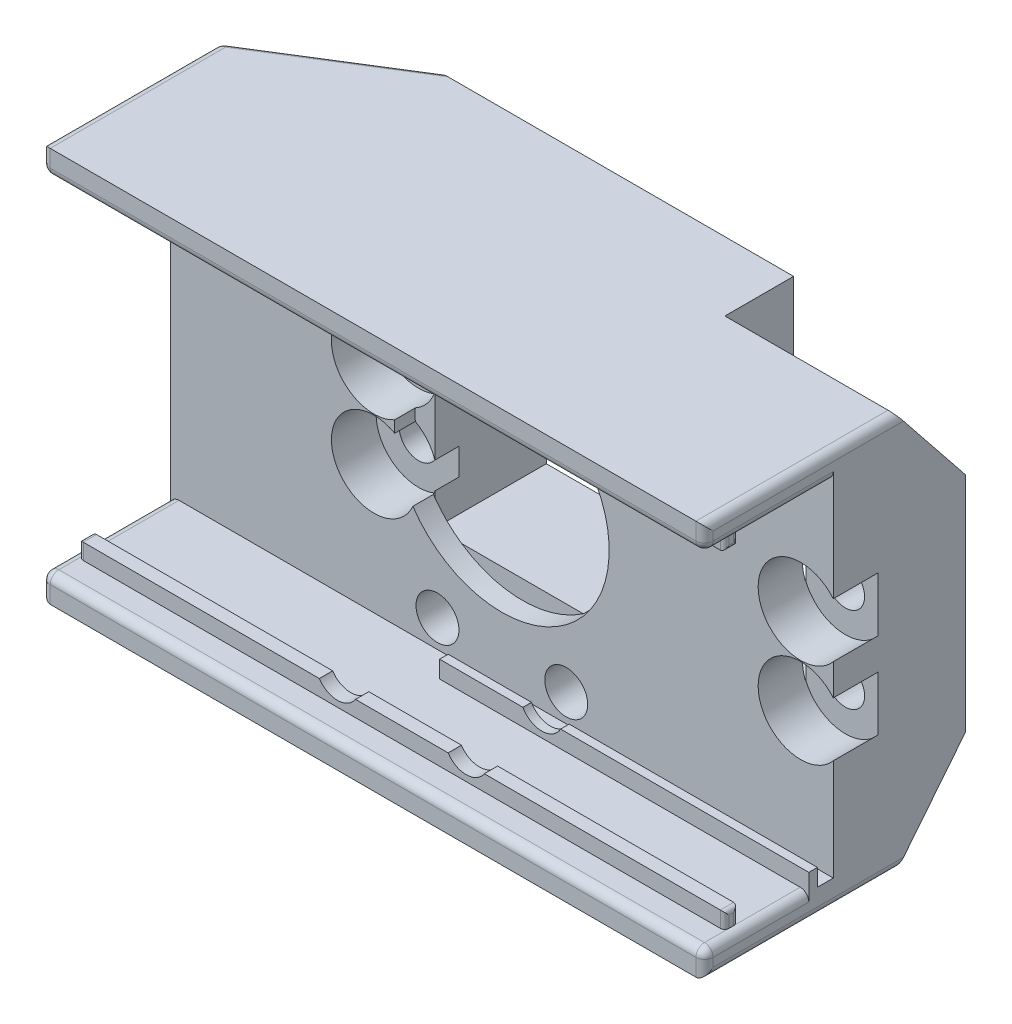
SolidWorks part; units mm, degrees
material "PLA"
ref_plane "Front Plane" through (0, 0, 0) normal (0, 0, 1) x (1, 0, 0)
ref_plane "Top Plane" through (0, 0, 0) normal (0, 1, 0) x (1, 0, 0)
ref_plane "Right Plane" through (0, 0, 0) normal (1, 0, 0) x (0, 0, -1)
sketch "Sketch2" plane through (0, 0, 0) normal (0, 0, 1) x (1, 0, 0)
  line L0 (-38.6, 0) -> (38.6, 0) construction
  line L1 (-38.6, 20) -> (38.6, 20)
  line L2 (-38.6, 20) -> (-38.6, -20)
  line L3 (-38.6, -20) -> (38.6, -20)
  line L4 (38.6, 20) -> (38.6, -20)
  line L5 (0, 20) -> (0, -20) construction
  circle A0 centre (0, 0) radius 12.5
  point P13 (0, 0)
  dimension "D1" = 25
  dimension "D2" = 40
  dimension "D3" = 77.2
extrude "Boss-Extrude1" add sketch "Sketch2" along normal blind 2.4
sketch "Sketch5" plane through (0, 0, 0) normal (0, 0, -1) x (-1, 0, 0)
  line L0 (38.6, -20) -> (-38.6, -20) construction
  line L1 (-30.2, 10.3) -> (10.2, 10.3)
  line L2 (-30.2, 10.3) -> (-30.2, -10.3)
  line L3 (-30.2, -10.3) -> (10.2, -10.3)
  line L4 (10.2, 10.3) -> (10.2, -10.3)
  line L5 (-38.6, 20) -> (21.7, 20)
  line L6 (-38.6, 20) -> (-38.6, -20)
  line L7 (-38.6, -20) -> (21.7, -20)
  line L8 (21.7, 20) -> (21.7, -20)
  point P4 (10.2, 0)
  point P13 (-30.2, 0)
  dimension "D1" = 10.2
  dimension "D2" = 30.2
  dimension "D3" = 11.5
  dimension "D4" = 20.6
extrude "Boss-Extrude4" add sketch "Sketch5" along normal blind 12.98
sketch "Sketch6" plane through (0, 0, -12.98) normal (0, 0, -1) x (-1, 0, 0)
  line L0 (-1000, 0) -> (49000, 0) construction
  line L1 (-36.1, -0.85) -> (-30.2, -0.85)
  line L2 (-36.1, -0.85) -> (-36.1, 0.85)
  line L3 (-36.1, 0.85) -> (-30.2, 0.85)
  line L4 (-30.2, -0.85) -> (-30.2, 0.85)
  line L5 (-30.2, 10.3) -> (-30.2, -10.3) construction
  line L7 (-10, -991.5845) -> (-10, 49008.4155) construction
  line L8 (-30.2, 10.3) -> (-30.2, -10.3) construction
  line L9 (16.1, -0.85) -> (10.2, -0.85)
  line L10 (16.1, -0.85) -> (16.1, 0.85)
  line L11 (16.1, 0.85) -> (10.2, 0.85)
  line L12 (10.2, -0.85) -> (10.2, 0.85)
  dimension "D1" = 1.7
  dimension "D2" = 5.9
  dimension "D3" = 0.85
  dimension "D4" = 20.2
extrude "Cut-Extrude1" cut sketch "Sketch6" against normal blind 3.5
sketch "Sketch9" plane through (0, 20, 0) normal (0, 1, 0) x (1, 0, 0)
  line L0 (-21.7, 12.98) -> (38.6, 12.98) construction
  line L1 (-38.6, 12.98) -> (4.4, 12.98)
  line L2 (-38.6, 12.98) -> (-38.6, -12.4)
  line L3 (-38.6, -12.4) -> (4.4, -12.4)
  line L4 (4.4, 12.98) -> (4.4, -12.4)
  line L5 (38.6, -2.4) -> (-38.6, -2.4) construction
  line L9 (-38.6, -2.4) -> (-38.6, 0) construction
  dimension "D1" = 10
  dimension "D2" = 43
extrude "Boss-Extrude7" add sketch "Sketch9" along normal blind 3
sketch "Sketch10" plane through (0, 20, 0) normal (0, -1, 0) x (1, 0, 0)
  line L0 (4.4, 12.4) -> (4.4, 2.4) construction
  line L1 (-38.6, 5.25) -> (4.4, 5.25)
  line L2 (-38.6, 5.25) -> (-38.6, 4.25)
  line L3 (-38.6, 4.25) -> (4.4, 4.25)
  line L4 (4.4, 5.25) -> (4.4, 4.25)
  line L6 (4.4, 2.4) -> (-38.6, 2.4) construction
  dimension "D1" = 1
  dimension "D2" = 1.85
extrude "Boss-Extrude8" add sketch "Sketch10" along normal blind 2
sketch "Sketch20" plane through (4.4, 0, 0) normal (1, 0, 0) x (0, 0, -1)
  line L1 (-12.4, 23) -> (12.98, 23)
  line L2 (-12.4, 23) -> (-12.4, 20)
  line L3 (-12.4, 20) -> (12.98, 20)
  line L4 (12.98, 23) -> (12.98, 20)
extrude "Boss-Extrude9" add sketch "Sketch20" along normal up to surface (34.2 mm away) up to face at (38.6, 0, -5.29)
hole_wizard "Ø4.0mm Dowel Hole1" positions "Sketch12" profile "Sketch13" hole size "Ø4.0" standard "ANSI Metric" end condition through all
sketch "Sketch12" plane through (0, 0, -12.98) normal (0, 0, -1) x (-1, 0, 0)
  line L5 (-38.6, 23) -> (-38.6, -20) construction
  line L7 (10.2, -10.3) -> (10.2, -0.85) construction
  point P0 (-34.8, 5)
  point P10 (-34.8, -5)
  point P12 (14.9, -5)
  point P14 (14.9, 5)
  dimension "D1" = 3.8
  dimension "D2" = 4.7
sketch "Sketch13" plane through (34.8, 5, -12.98) normal (1, 0, 0) x (0, 1, 0)
  line L0 (0, 0) -> (0, 25.38)
  line L1 (0, 25.38) -> (2.25, 25.38)
  line L2 (2.25, 25.38) -> (2.25, 0)
  line L5 (2.25, 0) -> (0, 0)
  line L11 (0, -6.35) -> (0, 107.95) construction
  dimension "Thru Hole Dia." = 4.5
  dimension "Thru Hole Depth" = 25.38
sketch "Sketch17" plane through (0, 0, -12.98) normal (0, 0, -1) x (-1, 0, 0)
  line L0 (-15, 20.3) -> (15, 20.3) construction
  line L1 (15, 20.3) -> (15, 10.3) construction
  line L2 (15, 10.3) -> (-15, 10.3) construction
  line L3 (-15, 10.3) -> (-15, 20.3) construction
  line L4 (10.2, 10.3) -> (-30.2, 10.3) construction
  point P2 (0, 10.3)
  dimension "D1" = 10
  dimension "D2" = 30
hole_wizard "Ø2.0mm Dowel Hole1" positions "Sketch18" profile "Sketch19" hole size "Ø2.0" standard "ANSI Metric" end condition through all
sketch "Sketch18" plane through (0, 0, -12.98) normal (0, 0, -1) x (-1, 0, 0)
  line L3 (-7.5, 16.8) -> (7.5, 16.8) construction
  line L6 (-38.6, 23) -> (38.6, 23) construction
  point P0 (-7.5, 16.8)
  point P2 (7.5, 16.8)
  point P16 (0, 16.8)
  dimension "D1" = 15
  dimension "D2" = 6.2
sketch "Sketch19" plane through (7.5, 16.8, -12.98) normal (1, 0, 0) x (0, 1, 0)
  line L0 (0, 0) -> (0, 25.38)
  line L1 (0, 25.38) -> (1.1, 25.38)
  line L2 (1.1, 25.38) -> (1.1, 0)
  line L5 (1.1, 0) -> (0, 0)
  line L11 (0, -6.35) -> (0, 107.95) construction
  dimension "Thru Hole Dia." = 2.2
  dimension "Thru Hole Depth" = 25.38
mirror "Mirror10" about plane through (0, 0, 0) normal (0, 1, 0) of "Ø2.0mm Dowel Hole1"
pattern_circular "CirPattern1" count 2 over 360 about axis through (0, 0, 0) along (0, 0, 1) of "Boss-Extrude7", "Boss-Extrude8"
sketch "Sketch14" plane through (0, 0, 2.4) normal (0, 0, 1) x (1, 0, 0)
  circle A0 centre (-14.9, 5) radius 4.95
  circle A1 centre (-14.9, -5) radius 4.95
  circle A2 centre (-7.5, 16.8) radius 2.5
  circle A3 centre (7.5, 16.8) radius 2.5
  circle A9 centre (34.8, 5) radius 4.95
  circle A11 centre (34.8, -5) radius 4.95
  circle A12 centre (-7.5, -16.8) radius 2.5
  circle A13 centre (7.5, -16.8) radius 2.5
  dimension "D1" = 9.9
  dimension "D2" = 5
extrude "Cut-Extrude2" cut sketch "Sketch14" against normal blind 5.2 and the other way through all
sketch "Sketch22" plane through (-4.4, 0, 0) normal (-1, 0, 0) x (0, 0, 1)
  line L0 (12.4, -23) -> (12.4, -20) construction
  line L1 (-12.98, -23) -> (12.4, -23)
  line L2 (-12.98, -23) -> (-12.98, -20)
  line L3 (-12.98, -20) -> (12.4, -20)
  line L4 (12.4, -23) -> (12.4, -20)
  line L5 (12.4, -20) -> (5.25, -20) construction
extrude "Boss-Extrude10" add sketch "Sketch22" along normal up to surface (34.2 mm away) up to face at (-38.6, 13.5, 1.8867)
sketch "Sketch28" plane through (0, 0, 12.4) normal (0, 0, 1) x (1, 0, 0)
  line L1 (-38.6, -20) -> (38.6, -20)
  line L2 (-38.6, -20) -> (-38.6, -23)
  line L4 (38.6, -20) -> (38.6, -23)
  line L6 (-38.6, -20) -> (38.6, -20) construction
  line L7 (38.6, -23) -> (38.6, -20) construction
  line L9 (-38.6, 20) -> (38.6, 20)
  line L10 (-38.6, 20) -> (-38.6, 23)
  line L12 (38.6, 20) -> (38.6, 23)
  line L14 (4.4, 20) -> (-38.6, 20) construction
  line L17 (-38.6, 23) -> (38.6, 23)
  line L18 (-38.6, -23) -> (38.6, -23)
extrude "Boss-Extrude15" add sketch "Sketch28" along normal blind 5 and the other way blind 1
fillet "Fillet6" radius 1 14 edges at (38.6, 23, 2.21) (38.6, 20, 9.9) (38.6, -23, 2.21) (38.6, -20, 11.325) (-38.6, -20, 9.9) (-38.6, -23, 2.21) (-38.6, -21.5, 17.4) (38.6, -21.5, 17.4) (0, -20, 17.4) (-38.6, 21.5, 17.4) (0, 20, 17.4) (38.6, 21.5, 17.4) (-38.6, 23, 2.21) (-38.6, 20, 11.325)
sketch "Sketch29" plane through (0, -20, 0) normal (0, 1, 0) x (1, 0, 0)
  line L0 (-37.6, -2.4) -> (-37.6, -16.4) construction
  line L1 (-37.6, -14.05) -> (37.6, -14.05)
  line L2 (-37.6, -14.05) -> (-37.6, -12.5)
  line L3 (-37.6, -12.5) -> (37.6, -12.5)
  line L4 (37.6, -14.05) -> (37.6, -12.5)
  line L5 (-37.6, -16.4) -> (37.6, -16.4) construction
  line L6 (37.6, -16.4) -> (37.6, -5.25) construction
  dimension "D2" = 1.55
  dimension "D3" = 2.35
extrude "Boss-Extrude16" add sketch "Sketch29" along normal blind 1.85
fillet "Fillet7" radius 0.5 6 edges at (37.6, -19.075, 12.5) (37.6, -18.15, 13.275) (37.6, -19.075, 14.05) (-37.6, -19.075, 12.5) (-37.6, -19.075, 14.05) (-37.6, -18.15, 13.275)
sketch "Sketch30" plane through (0, 20, 0) normal (0, -1, 0) x (1, 0, 0)
  line L0 (37.6, 2.4) -> (37.6, 16.4) construction
  line L1 (37.6, 12.5) -> (-37.6, 12.5)
  line L2 (37.6, 12.5) -> (37.6, 14.05)
  line L3 (37.6, 14.05) -> (-37.6, 14.05)
  line L4 (-37.6, 12.5) -> (-37.6, 14.05)
  line L5 (37.6, 16.4) -> (-37.6, 16.4) construction
  line L6 (-37.6, 16.4) -> (-37.6, 5.25) construction
  dimension "D2" = 1.55
  dimension "D3" = 2.35
extrude "Boss-Extrude17" add sketch "Sketch30" along normal blind 1.85
fillet "Fillet8" radius 0.5 6 edges at (37.6, 19.075, 12.5) (37.6, 18.15, 13.275) (37.6, 19.075, 14.05) (-37.6, 19.075, 12.5) (-37.6, 18.15, 13.275) (-37.6, 19.075, 14.05)
sketch "Sketch31" plane through (0, 0, 14.05) normal (0, 0, 1) x (1, 0, 0)
  circle A0 centre (7.5, -16.8) radius 2.5 construction
  circle A1 centre (-7.5, -16.8) radius 2.5 construction
  circle A2 centre (7.5, 16.8) radius 2.5 construction
  circle A3 centre (-7.5, 16.8) radius 2.5 construction
  circle A4 centre (7.5, -16.8) radius 2.5
  circle A5 centre (-7.5, -16.8) radius 2.5
  circle A6 centre (7.5, 16.8) radius 2.5
  circle A7 centre (-7.5, 16.8) radius 2.5
extrude "Cut-Extrude4" cut sketch "Sketch31" against normal up to surface (1.55 mm away) up to face at (0, 19.075, 12.5)
sketch "Sketch32" plane through (38.6, 0, 0) normal (1, 0, 0) x (0, 0, -1)
  line L0 (4.98, -23) -> (12.98, -13)
  line L2 (12.98, -13) -> (12.98, -23)
  line L3 (12.98, -23) -> (4.98, -23)
  line L4 (4.98, 23) -> (12.98, 13)
  line L7 (12.98, 13) -> (12.98, 23)
  line L8 (12.98, 23) -> (4.98, 23)
  dimension "D1" = 10
  dimension "D2" = 8
  dimension "D3" = 8
  dimension "D4" = 10
extrude "Cut-Extrude5" cut sketch "Sketch32" against normal blind 20
sketch "Sketch35" plane through (0, 23, 0) normal (0, 1, 0) x (1, 0, 0)
  line L0 (-38.6, 12.98) -> (-38.6, 2.98)
  line L1 (-38.6, 2.98) -> (-22.6, 12.98)
  line L3 (-22.6, 12.98) -> (-38.6, 12.98)
  dimension "D1" = 16
  dimension "D2" = 10
extrude "Cut-Extrude6" cut sketch "Sketch35" against normal through all
fillet "Fillet10" radius 0.5 3 edges at (-30.1, 23, -8.2925) (-38.6, 21, -2.98) (-38.3071, 22.7071, -3.1631)
sketch "Sketch36" plane through (0, 0, 2.4) normal (0, 0, 1) x (1, 0, 0)
  circle A0 centre (0, 0) radius 6.5145
ref_point "Point1"
sketch "Sketch37" plane through (0, 0, 0) normal (0, 0, -1) x (-1, 0, 0)
  line L0 (-7.1246, -10.2708) -> (-7.1246, -10.3)
  line L1 (-7.1246, 10.3) -> (-30.2, 10.3)
  line L2 (-7.1246, 10.3) -> (-7.1246, 10.2708)
  line L3 (-7.1246, -10.3) -> (-30.2, -10.3)
  line L4 (-30.2, 10.3) -> (-30.2, -10.3)
  line L5 (-7.1246, 10.3) -> (-30.2, -10.3) construction
  line L6 (-7.1246, -10.3) -> (-30.2, 10.3) construction
  arc A0 (-7.1246, -10.2708) -> (-7.1246, 10.2708) centre (0, 0) ccw
  point P0 (-18.6623, 0)
  arc M1 (-30.2, 6.8283) -> (-30.2, 3.1717) centre (-34.8, 5) cw
  line M2 (-30.2, 3.1717) -> (-30.2, -3.1717)
  arc M3 (-30.2, -3.1717) -> (-30.2, -6.8283) centre (-34.8, -5) cw
  line M4 (-30.2, -6.8283) -> (-30.2, -10.3)
  line M5 (-30.2, -10.3) -> (-7.0824, -10.3)
  arc M6 (-7.0824, -10.3) -> (-7.0824, 10.3) centre (0, 0) cw
  line M7 (-7.0824, 10.3) -> (-30.2, 10.3)
  line M8 (-30.2, 10.3) -> (-30.2, 6.8283)
  dimension "D3" = 25
  dimension "D1" = 11.5377
  dimension "D2" = 10.3
extrude "Boss-Extrude20" add sketch "Sketch37" along normal blind 2.75 contours L2 L0 M7 M8 M1 M2 M3 M4 M5 M6
